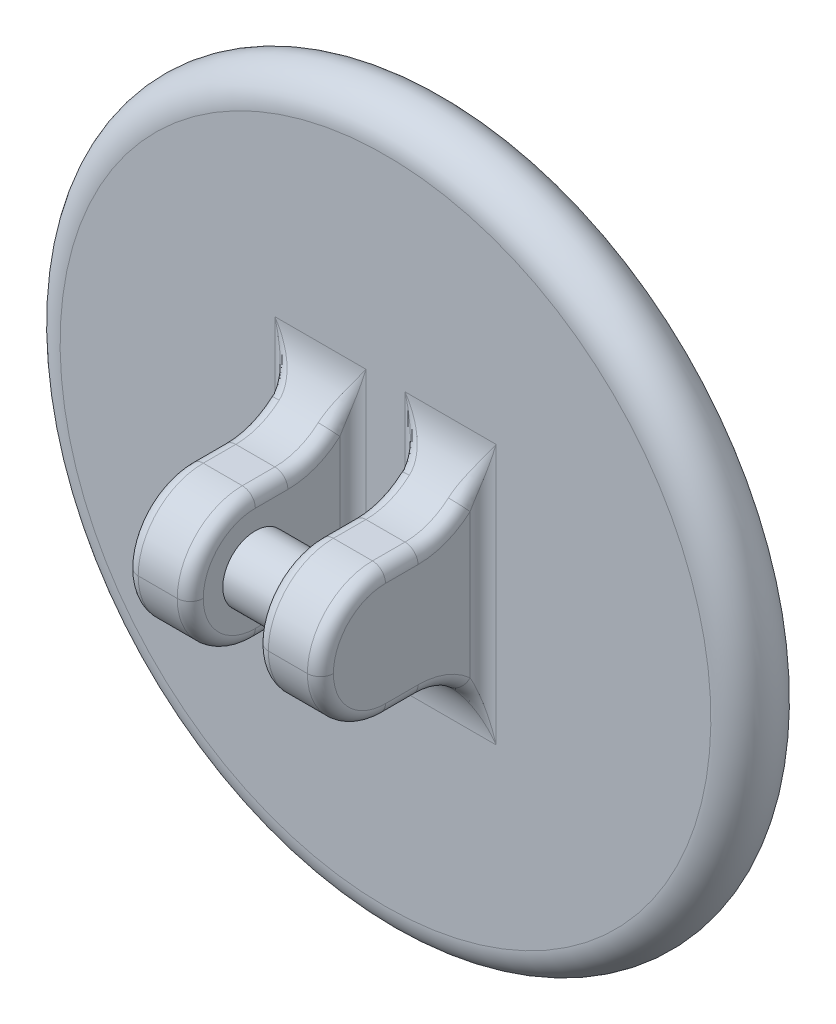
SolidWorks part; units mm, degrees
ref_plane "Front Plane" through (0, 0, 0) normal (0, 0, 1) x (1, 0, 0)
ref_plane "Top Plane" through (0, 0, 0) normal (0, 1, 0) x (1, 0, 0)
ref_plane "Right Plane" through (0, 0, 0) normal (1, 0, 0) x (0, 0, -1)
sketch "Sketch1" plane through (0, 0, 0) normal (0, 0, 1) x (1, 0, 0)
  line L0 (0, 0) -> (-250, 0)
  line L1 (-250, 50) -> (0, 50)
  line L2 (0, 50) -> (0, 0)
  arc A0 (-250, 50) -> (-250, 0) centre (-250, 25) ccw
  dimension "D1" = 250
  dimension "D3" = 50
revolve "Revolve1" add sketch "Sketch1" angle 360 about L2
sketch "Sketch2" plane through (0, 50, 0) normal (0, 1, 0) x (1, 0, 0)
  line L0 (-207.9821, 0) -> (207.9821, 0)
  line L1 (0, -207.7443) -> (0, 207.7443)
  line L2 (-75, -50) -> (-25, -50)
  line L3 (-75, -50) -> (-75, 50)
  line L4 (-75, 50) -> (-25, 50)
  line L5 (-25, -50) -> (-25, 50)
  line L6 (-75, -50) -> (-25, 50) construction
  line L7 (-75, 50) -> (-25, -50) construction
  line L8 (75, 50) -> (25, 50)
  line L9 (25, -50) -> (25, 50)
  line L10 (75, -50) -> (25, -50)
  line L11 (75, -50) -> (75, 50)
  point P0 (-50, 0)
  point P4 (0, 0)
  point P13 (0, 0)
  dimension "D3" = 50
  dimension "D1" = 25
extrude "Boss-Extrude1" add sketch "Sketch2" along normal blind 125 contours L5 L4 L3 L2 | L9 L8 L11 L10
sketch "Sketch3" plane through (-75, 0, 0) normal (-1, 0, 0) x (0, 0, 1)
  line L1 (50, 175) -> (-50, 175) construction
  line L2 (50, 50) -> (-50, 50) construction
  line L3 (50, 175) -> (50, 50) construction
  circle A0 centre (0, 125) radius 25
  dimension "D3" = 50
  dimension "D1" = 50
  dimension "D2" = 50
fillet "Fillet1" radius 50 4 edges at (50, 50, -50) (-50, 50, -50) (50, 50, 50) (-50, 50, 50)
fillet "Fillet2" radius 50 4 edges at (-50, 175, -50) (50, 175, -50) (50, 175, 50) (-50, 175, 50)
fillet "Fillet3" radius 10 4 edges at (75, 50, 0) (-75, 50, 0) (25, 50, 0) (-25, 50, 0)
fillet "Fillet4" radius 10 32 edges at (-76.2598, 55.1412, 77.9164) (-75, 77.6393, 55.2786) (-76.2598, 55.1412, -77.9164) (-75, 77.6393, -55.2786) (-75, 160.3553, -35.3553) (23.7402, 55.1412, 77.9164) (25, 77.6393, 55.2786) (23.7402, 55.1412, -77.9164) (25, 77.6393, -55.2786) (25, 160.3553, -35.3553) (76.2598, 55.1412, -77.9164) (75, 77.6393, -55.2786) (75, 160.3553, -35.3553) (76.2598, 55.1412, 77.9164) (75, 77.6393, 55.2786) (-23.7402, 55.1412, -77.9164) (-25, 77.6393, -55.2786) (-25, 160.3553, -35.3553) (-23.7402, 55.1412, 77.9164) (-25, 77.6393, 55.2786) (-75, 160.3553, 35.3553) (25, 160.3553, 35.3553) (75, 160.3553, 35.3553) (-25, 160.3553, 35.3553) (-75, 112.5, 50) (-75, 112.5, -50) (25, 112.5, 50) (25, 112.5, -50) (75, 112.5, -50) (75, 112.5, 50) (-25, 112.5, -50) (-25, 112.5, 50)
extrude "Boss-Extrude2" add sketch "Sketch3" against normal up to surface (150 mm away) up to face at (75, 106.9643, 0)
sketch "Sketch4" plane through (0, 0, 0) normal (1, 0, 0) x (0, 0, -1)
  circle A0 centre (0, 125) radius 25 construction
  circle A1 centre (0, 125) radius 25 construction
  point P3 (0, 125)
  point P4 (0, 0)
  point P5 (0, 125)
ref_point "Point1"
move or copy body "Body-Move/Copy1" bodies to move or copy 104 copy no translate (0, -125, 0)
move or copy body "Body-Move/Copy2" bodies to move or copy 105 copy no rotation origin (0, 0, 0) rotation axis (1, 0, 0) rotation angle 90
equation "\"D2@Sketch3\"=\"D2@Sketch2\"/2"
equation "\"D3@Sketch3\"=\"D2@Sketch3\""
